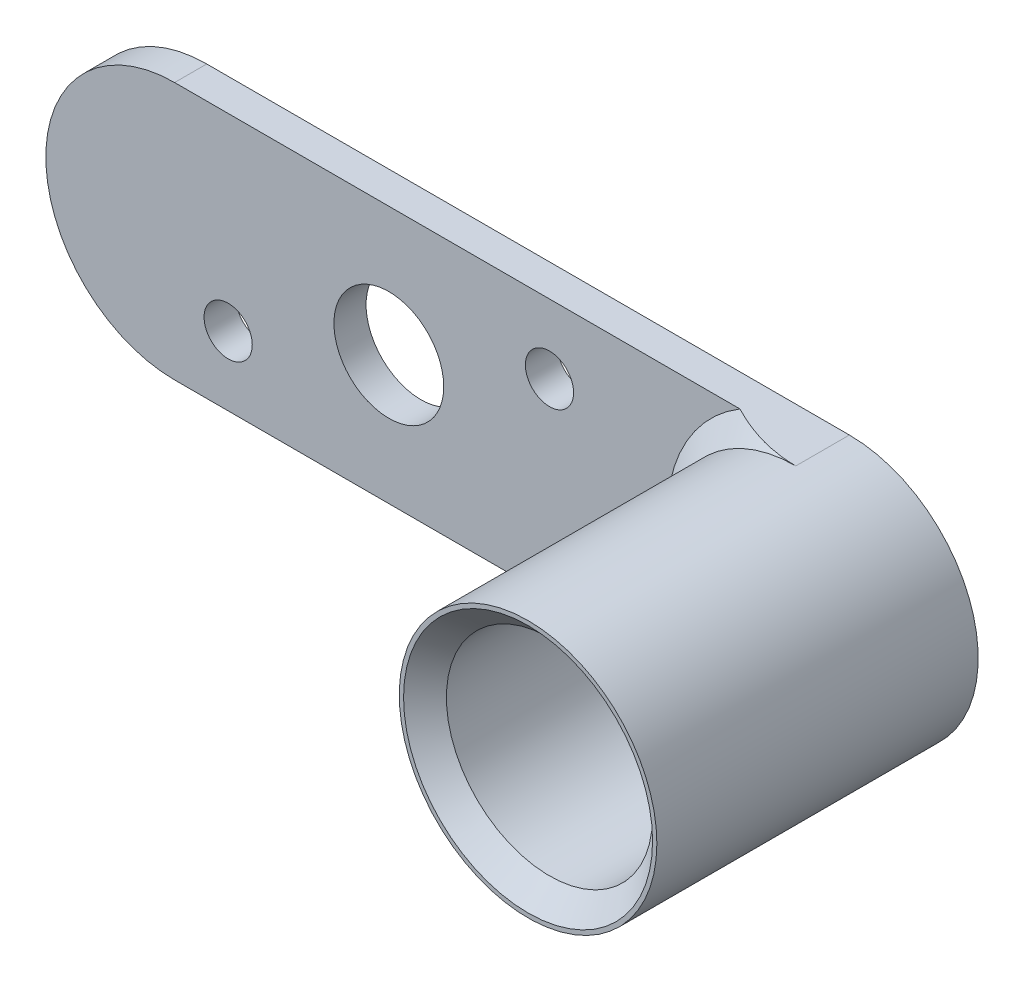
SolidWorks part; units mm, degrees
ref_plane "前视基准面" through (0, 0, 0) normal (0, 0, 1) x (1, 0, 0)
ref_plane "上视基准面" through (0, 0, 0) normal (0, 1, 0) x (1, 0, 0)
ref_plane "右视基准面" through (0, 0, 0) normal (1, 0, 0) x (0, 0, -1)
sketch "草图1" plane through (0, 0, 0) normal (0, 0, 1) x (1, 0, 0)
  line L0 (-15, -5.5678) -> (15, 5.5678) construction
  line L1 (40, 12.025) -> (-20, 12.025)
  line L3 (40, -12.025) -> (-20, -12.025)
  line L5 (-32.025, 0) -> (40, 0) construction
  line L6 (0, 16) -> (0, -16) construction
  arc A0 (-20, 12.025) -> (-20, -12.025) centre (-20, 0) ccw
  circle A3 centre (0, 0) radius 5.125
  circle A4 centre (0, 0) radius 16 construction
  circle A5 centre (-15, -5.5678) radius 2.25
  circle A6 centre (15, 5.5678) radius 2.25
  circle A8 centre (40, 0) radius 9.625
  circle A9 centre (40, 0) radius 12.025
  dimension "D2" = 60
  dimension "D3" = 30
  dimension "D6" = 10.25
  dimension "D7" = 32
  dimension "D8" = 4.5
  dimension "D11" = 19.25
  dimension "D12" = 2.4
  dimension "D5" = 40
extrude "凸台-拉伸1" add sketch "草图1" along normal blind 3 contours A9 L1 A0 L3 A3 A5 A6 | A9 A8 region at (27.2157, 0, 0) region at (48.2625, 8.2625, 0)
extrude "凸台-拉伸2" add sketch "草图1<3>" along normal blind 30 contours A9 A8 region at (48.2625, 8.2625, 0)
sketch "草图1<3>" plane through (0, 0, 0) normal (0, 0, 1) x (1, 0, 0) same geometry as "草图1"
chamfer "倒角1" distance 2 angle 45 3 edges at (49.625, 0, 0) (49.625, 0, 30) (27.975, 0, 3)
